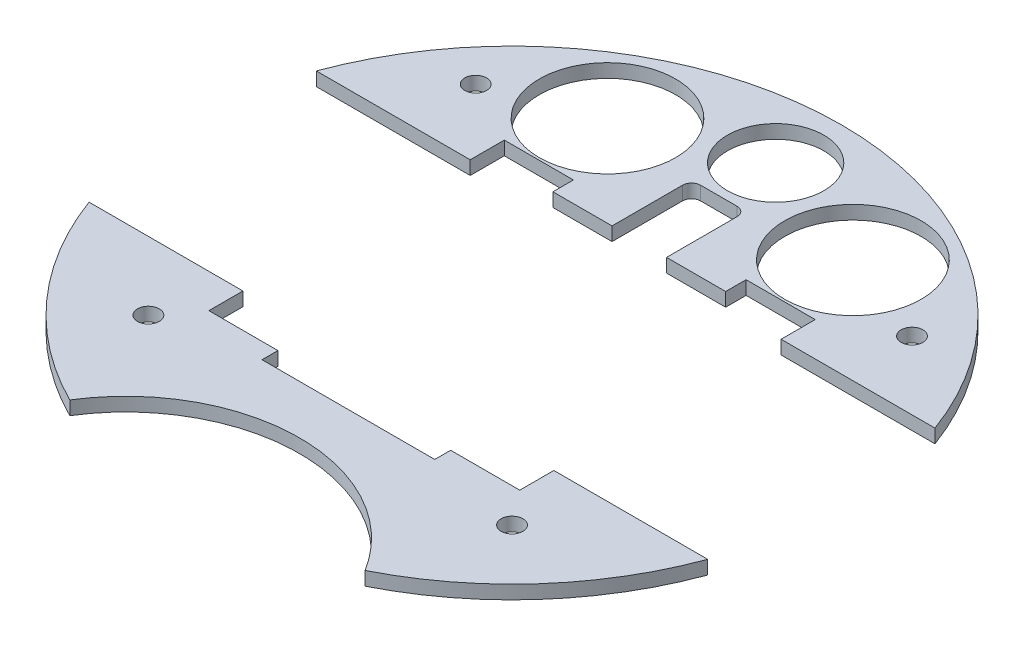
SolidWorks part; units mm, degrees
material "ABS"
ref_plane "Front Plane" through (0, 0, 0) normal (0, 0, 1) x (1, 0, 0)
ref_plane "Top Plane" through (0, 0, 0) normal (0, 1, 0) x (1, 0, 0)
ref_plane "Right Plane" through (0, 0, 0) normal (1, 0, 0) x (0, 0, -1)
sketch "Sketch1" plane through (0, 0, 0) normal (0, 1, 0) x (1, 0, 0)
  line L0 (0, -85) -> (-32.4891, -64.8129) construction
  line L1 (0, -85) -> (0, 0) construction
  arc A0 (32.4891, -64.8129) -> (-32.4891, -64.8129) centre (0, 0) ccw
  arc A1 (32.4891, -64.8129) -> (-32.4891, -64.8129) centre (0, -85) ccw
  dimension "D1" = 145
  dimension "D2" = 76.5
  dimension "D3" = 85
extrude "Boss-Extrude1" add sketch "Sketch1" along normal blind 3
sketch "solenoid placement" plane through (0, 3, 0) normal (0, 1, 0) x (1, 0, 0)
  line L4 (-19, -36) -> (19, -36)
  line L5 (-19, 28) -> (-19, -36)
  line L10 (19, 28) -> (-19, 28)
  line L11 (19, -36) -> (19, 28)
  line L12 (-19, -36) -> (19, -36)
  line L13 (-19, 28) -> (-19, -36)
  line L14 (19, 28) -> (-19, 28)
  line L15 (19, -36) -> (19, 28)
  dimension "D1" = 0
extrude "Cut-Extrude1" cut sketch "solenoid placement" against normal through all
sketch "Sketch7" plane through (0, 3, 0) normal (0, 1, 0) x (1, 0, 0)
  circle A3 centre (27, 48) radius 15
  circle A4 centre (27, 48) radius 15
  circle A5 centre (-27, 48) radius 15
  circle A6 centre (-27, 48) radius 15
  dimension "D1" = 0
  dimension "D2" = 0
extrude "Cut-Extrude6" cut sketch "Sketch7" against normal through all
sketch "Sketch8" plane through (0, 3, 0) normal (0, 1, 0) x (1, 0, 0)
  circle A1 centre (40, -40) radius 2.4
  circle A2 centre (40, -40) radius 2.4
  circle A3 centre (-40, -40) radius 2.4
  circle A4 centre (-40, -40) radius 2.4
  circle A5 centre (48, 40) radius 2.4
  circle A6 centre (48, 40) radius 2.4
  circle A7 centre (-48, 40) radius 2.4
  circle A8 centre (-48, 40) radius 2.4
  dimension "D1" = 0
  dimension "D2" = 0
  dimension "D3" = 0
  dimension "D4" = 0
extrude "Cut-Extrude7" cut sketch "Sketch8" against normal through all
sketch "Sketch3" plane through (0, 3, 0) normal (0, 1, 0) x (1, 0, 0)
  line L1 (-34.2, -32.5) -> (-22.2, -32.5)
  line L2 (-34.2, 25) -> (-68.0533, 25)
  line L3 (-34.2, 32.5) -> (-22.2, 32.5)
  line L4 (-22.2, -32.5) -> (-22.2, 32.5) construction
  line L8 (0, 0) -> (0, 72.5) construction
  line L17 (-34.2, -32.5) -> (-34.2, -25)
  line L18 (-34.2, -25) -> (-68.0533, -25)
  line L19 (-34.2, 25) -> (-34.2, 32.5)
  line L21 (-22.2, 32.5) -> (-19, 32.5)
  line L22 (-22.2, 32.5) -> (-22.2, -32.5) construction
  line L23 (-22.2, -32.5) -> (-19, -32.5)
  line L24 (-19, 32.5) -> (-19, -32.5)
  line L25 (22.2, 32.5) -> (22.2, -32.5) construction
  line L26 (22.2, -32.5) -> (22.2, 32.5) construction
  line L27 (19, 32.5) -> (19, -32.5)
  line L28 (22.2, -32.5) -> (19, -32.5)
  line L29 (22.2, 32.5) -> (19, 32.5)
  line L30 (34.2, 25) -> (34.2, 32.5)
  line L31 (34.2, -25) -> (68.0533, -25)
  line L32 (34.2, -32.5) -> (34.2, -25)
  line L33 (34.2, 32.5) -> (22.2, 32.5)
  line L34 (34.2, 25) -> (68.0533, 25)
  line L35 (34.2, -32.5) -> (22.2, -32.5)
  line L36 (-19, 28) -> (-19, -36) construction
  arc A0 (32.4891, -64.8129) -> (-32.4891, -64.8129) centre (0, 0) ccw construction
  arc A2 (68.0533, 25) -> (68.0533, -25) centre (0, 0) cw
  arc A3 (-68.0533, 25) -> (-68.0533, -25) centre (0, 0) ccw
  point P31 (-34.2, -32.5)
  dimension "D1" = 50
extrude "Cut-Extrude3" cut sketch "Sketch3" against normal through all
sketch "Sketch9" plane through (0, 3, 0) normal (0, 1, 0) x (1, 0, 0)
  line L0 (6, 43.5) -> (6, 28)
  line L1 (-6, 43.5) -> (-6, 28)
  line L2 (19, 28) -> (-19, 28) construction
  line L8 (-6, 28) -> (6, 28)
  line L10 (4, 45.5) -> (-4, 45.5)
  arc A0 (-6, 43.5) -> (-4, 45.5) centre (-4, 43.5) cw
  arc A1 (6, 43.5) -> (4, 45.5) centre (4, 43.5) ccw
  point P5 (0, 28)
  point P6 (0, 28)
  point P16 (-6, 45.5)
  point P19 (6, 45.5)
  dimension "D3" = 2
  dimension "D2" = 12
  dimension "D1" = 17.5
extrude "Cut-Extrude8" cut sketch "Sketch9" against normal through all
sketch "Sketch10" plane through (0, 3, 0) normal (0, 1, 0) x (1, 0, 0)
  line L0 (0, 0) -> (0, 58) construction
  circle A0 centre (0, 58) radius 10.605
  dimension "D1" = 21.21
  dimension "D2" = 58
extrude "Cut-Extrude9" cut sketch "Sketch10" against normal through all
equation "\"smallPulleyTeeth\"= 30"
equation "\"largePulleyTeeth\"= 30"
equation "\"eighthThick\"= 3.0mm"
equation "\"sixteenthThick\"= 1.7mm"
equation "\"quarterThick\"=6.0mm"
equation "\"OD\"= 145mm"
equation "\"puckAngle\"= 60.5deg"
equation "\"D1@Sketch1\"=\"OD\""
equation "\"puckDiam\"= 76.5mm"
equation "\"D2@Sketch1\"=\"puckDiam\""
equation "\"D1@Boss-Extrude1\"=\"eighthThick\""
equation "\"axlePress\"= 5.9mm"
equation "\"press\"= 0.2mm"
equation "\"wheelClear\"= 0.3mm"
equation "\"10-32clear\"= 4.8mm"
equation "\"6-32clear\"= 3.3mm"
equation "\"8-32clear\"= 4.0mm"
equation "\"4-40clear\"= 3.0mm"
equation "\"wheelHeight\"= 22mm"
equation "\"wheelWell\"= 65mm"
equation "\"puckDist\"= 85mm"
equation "\"D3@Sketch1\"=\"puckDist\""
equation "\"scoopFillet\"= 5mm"
